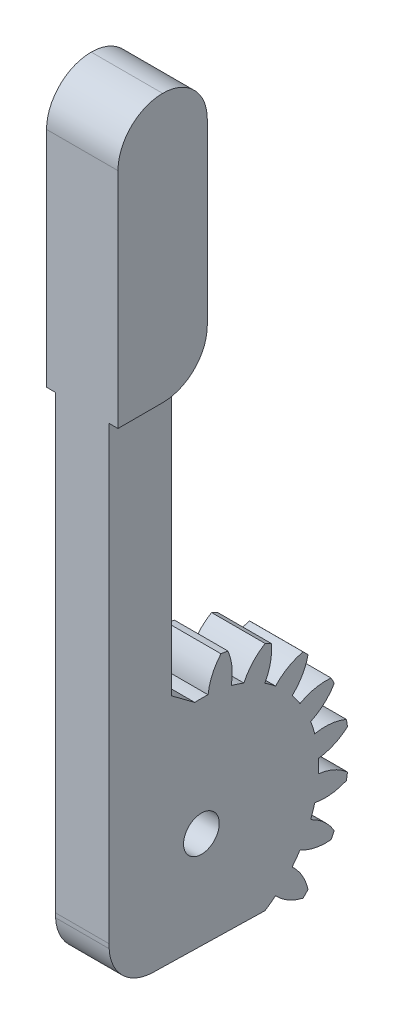
SolidWorks part; units mm, degrees
ref_plane "Plane1" through (0, 0, 0) normal (0, 0, 1) x (1, 0, 0)
ref_plane "Plane2" through (0, 0, 0) normal (0, 1, 0) x (1, 0, 0)
ref_plane "Plane3" through (0, 0, 0) normal (1, 0, 0) x (0, 0, -1)
other "Configuration Table"
sketch "HoldingSke" plane through (0, 0, 0) normal (0, 1, 0) x (1, 0, 0)
  line L0 (0, 0) -> (0.6265, -0.228)
  line L1 (-15, 0) -> (100, 0) construction
  line L2 (0, 0) -> (-2.1039, 2.3779)
  line L3 (0, 0) -> (-11.863, 4.5341)
  line L4 (0, 0) -> (8.1152, 2.9537)
  line L5 (0, 0) -> (-46.8476, -17.4728)
  line L6 (0, 0) -> (-4.9738, -3.3558)
  line L7 (-2.1039, 2.3779) -> (8.6586, 51.2059)
  line L8 (-76.2, 54.61) -> (-75.5, 54.61)
  line L9 (-71.009, 38.7566) -> (-53.1078, 45.2721)
  line L10 (-76.2, 71.12) -> (104.1128, 71.12)
  line L11 (0, 0) -> (-6, 0)
  line L12 (-76.2, 101.6) -> (-76.147, 101.6)
  line L13 (24.9733, 27.94) -> (52.9518, 28.4284)
  line L14 (24.9733, 27.94) -> (24.9743, 27.94)
  line L15 (24.9733, 27.94) -> (100.4006, 29.5858)
  line L16 (-63.627, -1.5) -> (-12.827, -1.5)
  circle A0 centre (0, 0) radius 2
  circle A1 centre (0, 0) radius 13.124
  circle A2 centre (0, 0) radius 37.5
  circle A3 centre (0, 0) radius 2
  dimension "Num_teeth" = 20
  dimension "Pitch_radius" = 180.3128
  dimension "Width" = 6
  dimension "Thickness" = 6
sketch "BasProSke" plane through (0, 0, 0) normal (0, 1, 0) x (1, 0, 0)
  line L0 (-10, 0) -> (60, 0) construction
  line L1 (0, 0) -> (0, 16.5)
  line L2 (0, 0) -> (6, 0)
  line L3 (6, 0) -> (6, 16.5)
  line L4 (6, 16.5) -> (0, 16.5)
  dimension "Thickness" = 6
  dimension "Diameter" = 33
revolve "Base-Revolve" add sketch "BasProSke" angle 360 about L0
sketch "TooCutSke" plane through (0, 0, 0) normal (1, 0, 0) x (0, 0, -1)
  line L1 (0, 0) -> (0, 107) construction
  line L2 (0, 0) -> (-1.2696, 14.9462) construction
  line L3 (0, 0) -> (-4.6808, 29.5532) construction
  line L4 (-1.2696, 14.9462) -> (-2.3404, 14.7766) construction
  arc A0 (0.7438, 13.1029) -> (-0.7438, 13.1029) centre (0, 0) ccw
  arc A1 (2.21, 16.377) -> (-2.21, 16.377) centre (0, 0) ccw
  circle A2 centre (0, 0) radius 15 construction
  circle A3 centre (0, 0) radius 14.0954 construction
  arc A4 (-0.7438, 13.1029) -> (-2.21, 16.377) centre (-6.7025, 12.3999) ccw
  arc A5 (2.21, 16.377) -> (0.7438, 13.1029) centre (6.7025, 12.3999) ccw
extrude "ToothCut" cut sketch "TooCutSke" along normal through all
fillet "Breaks" [suppressed] radius 0.03 tangent propagation no
fillet "RootFillets" [suppressed] radius 0.376
pattern_circular "TeethCuts" count 20 every 18 about axis through (-10, 0, 0) along (1, 0, 0) of "ToothCut", "RootFillets", "Breaks"
sketch "HubNeaOneSke" plane through (0, 0, 0) normal (-1, 0, 0) x (0, 0, 1)
  circle A0 centre (0, 0) radius 13.124
  dimension "Diameter" = 26.248
extrude "HubNearOne" [suppressed] add sketch "HubNeaOneSke" along normal blind 44.0001
sketch "HubNeaBotSke" plane through (0, 0, 0) normal (-1, 0, 0) x (0, 0, 1)
  circle A0 centre (0, 0) radius 13.124
  dimension "Diameter" = 26.248
extrude "HubNearBoth" [suppressed] add sketch "HubNeaBotSke" along normal blind 22
ref_plane "FarPln" through (6, 0, 0) normal (1, 0, 0) x (0, 0, -1)
sketch "HubFarSke" plane through (6, 0, 0) normal (1, 0, 0) x (0, 0, -1)
  circle A0 centre (0, 0) radius 13.124
  dimension "Diameter" = 26.248
extrude "HubFar" [suppressed] add sketch "HubFarSke" along normal blind 22
sketch "BorSke" plane through (0, 0, 0) normal (1, 0, 0) x (0, 0, -1)
  circle A0 centre (0, 0) radius 2
  dimension "Diameter" = 4
extrude "Bore" cut sketch "BorSke" along normal mid plane 100.0001
sketch "KeySke" plane through (0, 0, 0) normal (1, 0, 0) x (0, 0, -1)
  line L0 (-0.8, 0) -> (-0.8, 2.7)
  line L1 (-0.8, 2.7) -> (0.8, 2.7)
  line L2 (0.8, 2.7) -> (0.8, 0)
  line L3 (0, 0) -> (0, 34) construction
  line L4 (-0.8, 0) -> (0.8, 0)
  dimension "Width" = 1.6
extrude "Keyway" [suppressed] cut sketch "KeySke" along normal mid plane 100.0001
pattern_circular "Keyway2" [suppressed] count 2 every 90 about axis through (-10, 0, 0) along (1, 0, 0)
ref_plane "Plane4" through (3, 0, 0) normal (1, 0, 0) x (0, 0, -1)
sketch "Sketch1" plane through (3, 0, 0) normal (1, 0, 0) x (0, 0, -1)
  line L1 (-3.3416, -16.7904) -> (-17.8736, -16.7904)
  line L2 (-3.3416, -16.7904) -> (-3.3416, 18.4353)
  line L3 (-3.3416, 18.4353) -> (-17.8736, 18.4353)
  line L4 (-17.8736, -16.7904) -> (-17.8736, 18.4353)
extrude "Cut-Extrude1" cut sketch "Sketch1" against normal mid plane 10
sketch "Sketch3" plane through (3, 0, 0) normal (1, 0, 0) x (0, 0, -1)
  line L1 (-3.3416, -15.0369) -> (-10.3416, -15.0369)
  line L2 (-3.3416, -15.0369) -> (-3.3416, 74.9631)
  line L3 (-3.3416, 74.9631) -> (-10.3416, 74.9631)
  line L4 (-10.3416, -15.0369) -> (-10.3416, 74.9631)
  point P4 (0, 0)
  dimension "D1" = 7
  dimension "D2" = 90
extrude "Boss-Extrude2" add sketch "Sketch3" along normal mid plane 6
sketch "Sketch4" plane through (3, 0, 0) normal (1, 0, 0) x (0, 0, -1)
  line L1 (-10.3416, 74.9631) -> (-0.3416, 74.9631)
  line L2 (-10.3416, 74.9631) -> (-10.3416, 44.9631)
  line L3 (-10.3416, 44.9631) -> (-0.3416, 44.9631)
  line L4 (-0.3416, 74.9631) -> (-0.3416, 44.9631)
  dimension "D1" = 10
  dimension "D2" = 30
extrude "Boss-Extrude3" add sketch "Sketch4" along normal mid plane 8
fillet "Fillet1" radius 10 1 edges at (3, -15.0369, 10.3416)
fillet "Fillet4" radius 5 3 edges at (3, 44.9631, 0.3416) (3, 74.9631, 10.3416) (3, 74.9631, 0.3416)
fillet "Fillet5" radius 1 1 edges at (3, 45.3806, 3.3416)
sketch "Sketch5" plane through (3, 0, 0) normal (1, 0, 0) x (0, 0, -1)
  line L0 (-0.7438, 13.1029) -> (-3.3416, 15.0369)
  line L1 (-3.3416, 15.0369) -> (-3.1939, 16.2412)
  line L2 (-3.1939, 16.2412) -> (-1.3259, 16.8848)
  line L3 (-1.3259, 16.8848) -> (-0.6468, 13.2333)
  line L4 (-0.6468, 13.2333) -> (-0.7438, 13.1029)
  point P8 (-3.1939, 16.2412)
  point P9 (-3.3416, 15.0369)
  point P10 (-3.3416, 15.0369)
extrude "Cut-Extrude4" cut sketch "Sketch5" against normal mid plane 8 contours L4 L3 L2 L1 L0 region at (3, 15.1841, 1.9243)
sketch "Sketch7" plane through (3, 0, 0) normal (1, 0, 0) x (0, 0, -1)
  line L0 (-4.9802, -17.4229) -> (10.3978, -17.4229)
  line L1 (10.3978, -17.4229) -> (7.5786, -11.0377)
  line L2 (7.5786, -11.0377) -> (-8.9032, -10.6646)
  line L3 (-4.9802, -17.4229) -> (-7.363, -15.2303)
  line L4 (-7.363, -15.2303) -> (-8.9032, -10.6646)
  arc A0 (-10.3416, -5.4975) -> (-3.3416, -15.0369) centre (-0.3416, -5.4975) ccw construction
  point P9 (-4.9802, -17.4229)
  point P11 (7.5786, -11.0377)
extrude "Cut-Extrude6" cut sketch "Sketch7" against normal mid plane 8 contours L4 L3 L0 L1 L2 region at (3, -14.1162, -0.655)
fillet "Fillet6" radius 5 1 edges at (3, -10.6646, 8.9032)
equation "' \"Module@HoldingSke\" = 6.35"
equation "' \"Num_teeth@HoldingSke\" = 12"
equation "' \"Ap@HoldingSke\" =  20"
equation "' \"Ap@HoldingSke\" = 20"
equation "' \"Width@HoldingSke\" = 0.5 * 25.4"
equation "' \"Hub_dia@HoldingSke\"= 1 * 25.4"
equation "' \"Hub_dia@HoldingSke\" = 1 * 25.4"
equation "' \"Overall_len@HoldingSke\" = 1.0 * 25.4"
equation "' \"Bore@HoldingSke\" = 0.75 * 25.4"
equation "' \"T_dim@HoldingSke\" = 0.1 * 25.4"
equation "' \"Width@KeySke\" = 0.25 * 25.4"
equation "' \"Show_teeth@HoldingSke\" = 13"
equation "' \"Backlash@HoldingSke\" = 0.009 * 25.4"
equation "' \"Addendum_fac@HoldingSke\" = 1.0"
equation "' \"Dedendum_fac@HoldingSke\" = 1.25"
equation "' \"Dedendum_add@HoldingSke\" = 0.00005 * 25.4"
equation "' \"Clearance_fac@HoldingSke\" = 0.25"
equation "\"Pitch@HoldingSke\" = 1 / \"Module@HoldingSke\""
equation "\"Overcut_dia@TooCutSke\" = (\"Num_teeth@HoldingSke\" + 2 * \"Addendum_fac@HoldingSke\") / \"Pitch@HoldingSke\" + 0.002 * 25.4"
equation "\"Pitch_dia@TooCutSke\" = \"Num_teeth@HoldingSke\" / \"Pitch@HoldingSke\""
equation "\"Base_dia@TooCutSke\" = \"Num_teeth@HoldingSke\" / \"Pitch@HoldingSke\" * cos((\"Ap@HoldingSke\"  * 3.14159265 / 180))"
equation "\"Root_dia@TooCutSke\" = (\"Num_teeth@HoldingSke\" + 2) / \"Pitch@HoldingSke\" - 2 * (\"Addendum_fac@HoldingSke\" + \"Dedendum_fac@HoldingSke\") / \"Pitch@HoldingSke\" - \"Dedendum_add@HoldingSke\" * 2"
equation "\"Half_ang@TooCutSke\" = 180 / \"Num_teeth@HoldingSke\""
equation "\"Half_CT@TooCutSke\" = \"Num_teeth@HoldingSke\" / \"Pitch@HoldingSke\" * sin((3.14159265 / 2 / \"Num_teeth@HoldingSke\")) / 2 - 7 * \"Backlash@HoldingSke\" / 4"
equation "\"Flank_rad@TooCutSke\" = \"Num_teeth@HoldingSke\" / \"Pitch@HoldingSke\" / 5"
equation "\"Radius@RootFillets\" = \"Clearance_fac@HoldingSke\" / \"Pitch@HoldingSke\" + \"Dedendum_add@HoldingSke\""
equation "\"Break_rad@Breaks\" = 0.02 / \"Pitch@HoldingSke\""
equation "\"Thickness@HoldingSke\" = \"Width@HoldingSke\""
equation "\"OAL@HoldingSke\" = \"Thickness@HoldingSke\""
equation "\"MHD@HoldingSke\" = (\"Num_teeth@HoldingSke\" + 2) / \"Pitch@HoldingSke\" - 2 * (\"Addendum_fac@HoldingSke\" + \"Dedendum_fac@HoldingSke\")  / \"Pitch@HoldingSke\" - \"Dedendum_add@HoldingSke\" * 2"
equation "\"MBD@HoldingSke\" = (\"Num_teeth@HoldingSke\" + 2) / \"Pitch@HoldingSke\" - 2 * (\"Addendum_fac@HoldingSke\" + \"Dedendum_fac@HoldingSke\")  / \"Pitch@HoldingSke\" - \"Dedendum_add@HoldingSke\" * 2 - 0.002 * 25.4"
equation "\"MHD@HoldingSke\" = ((sgn( \"MHD@HoldingSke\" - \"Hub_dia@HoldingSke\" )-1)*( \"MHD@HoldingSke\" - \"Hub_dia@HoldingSke\" ))/-2+ \"Hub_dia@HoldingSke\""
equation "\"MBD@HoldingSke\" = ((sgn( \"MBD@HoldingSke\" - \"Bore@HoldingSke\" )-1)*( \"MBD@HoldingSke\" - \"Bore@HoldingSke\" ))/-2+ \"Bore@HoldingSke\""
equation "\"OAL@HoldingSke\" = ((sgn( \"OAL@HoldingSke\" - \"Overall_len@HoldingSke\" )+1)*( \"OAL@HoldingSke\" - \"Overall_len@HoldingSke\" ))/2 + \"Overall_len@HoldingSke\" + 0.000002 * 25.4"
equation "\"Num_teeth@TeethCuts\" = int( \"Show_teeth@HoldingSke\" ) + 1"
equation "\"Num_teeth@TeethCuts\" = ((sgn( \"Num_teeth@TeethCuts\" - \"Num_teeth@HoldingSke\" )-1)*( \"Num_teeth@TeethCuts\" - \"Num_teeth@HoldingSke\" ))/-2+ \"Num_teeth@HoldingSke\""
equation "\"Num_teeth@TeethCuts\" = ((sgn( \"Num_teeth@TeethCuts\" - 2.0)+1)*( \"Num_teeth@TeethCuts\" - 2.0))/2 +2.0"
equation "\"Angle@TeethCuts\" = 360.0 / \"Num_teeth@HoldingSke\""
equation "\"Diameter@BasProSke\" = (\"Num_teeth@HoldingSke\" + 2 * \"Addendum_fac@HoldingSke\") / \"Pitch@HoldingSke\""
equation "\"Thickness@BasProSke\"  = \"Thickness@HoldingSke\""
equation "' \"Fillet_rad@BasProSke\" =  \"Thickness@HoldingSke\" * 0.05"
equation "' \"Fillet_rad@BasProSke\" = \"Thickness@HoldingSke\" * 0.05"
equation "\"MHD@HoldingSke\" = ((sgn( \"MHD@HoldingSke\" - \"Root_dia@TooCutSke\" )-1)*( \"MHD@HoldingSke\" - \"Root_dia@TooCutSke\" ))/-2+ \"Root_dia@TooCutSke\""
equation "\"Diameter@HubNeaOneSke\" = \"MHD@HoldingSke\""
equation "\"Length@HubNearOne\" = \"OAL@HoldingSke\" - \"Thickness@BasProSke\""
equation "\"Diameter@HubNeaBotSke\" = \"MHD@HoldingSke\""
equation "\"Length@HubNearBoth\" = ( \"OAL@HoldingSke\" - \"Thickness@BasProSke\" ) / 2.0"
equation "\"Thickness@FarPln\" = \"Thickness@BasProSke\""
equation "\"Diameter@HubFarSke\" = \"MHD@HoldingSke\""
equation "\"Length@HubFar\" = ( \"OAL@HoldingSke\" - \"Thickness@BasProSke\" ) / 2.0"
equation "\"Diameter@BorSke\" = \"MBD@HoldingSke\""
equation "\"D1@Bore\" = \"OAL@HoldingSke\" * 2.0"
equation "\"D1@Keyway\" = \"OAL@HoldingSke\" * 2.0"
equation "\"Offset@KeySke\" = \"T_dim@HoldingSke\" + \"MBD@HoldingSke\" / 2.0"
